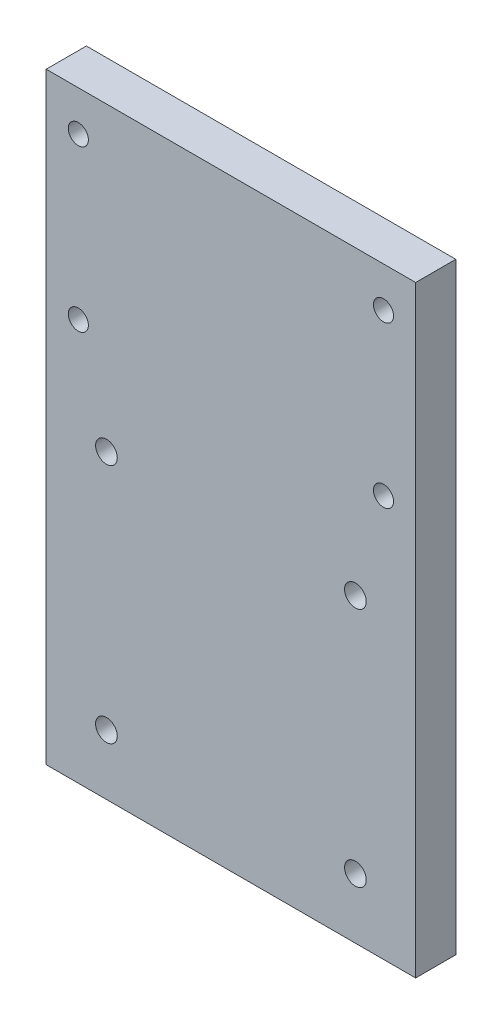
SolidWorks part; units mm, degrees
ref_plane "前基準面" through (0, 0, 0) normal (0, 0, 1) x (1, 0, 0)
ref_plane "上基準面" through (0, 0, 0) normal (0, 1, 0) x (1, 0, 0)
ref_plane "右基準面" through (0, 0, 0) normal (1, 0, 0) x (0, 0, -1)
ref_axis "基準軸1" through (0, -55, 0) along (0, 1, 0)
ref_axis "基準軸2" through (-88.99, 0, 0) along (1, 0, 0)
ref_axis "基準軸3" through (0, 0, 55) along (0, 0, -1)
sketch "草圖1" plane through (0, 0, 0) normal (0, 0, 1) x (1, 0, 0)
  line L0 (0, -41.25) -> (0, 41.25) construction
  line L1 (-23, -37.5) -> (23, -37.5)
  line L2 (-23, -37.5) -> (-23, 37.5)
  line L3 (-23, 37.5) -> (23, 37.5)
  line L4 (23, -37.5) -> (23, 37.5)
  line L5 (25.3, 0) -> (-25.3, 0) construction
  circle A0 centre (-19, 32.5) radius 1.25
  circle A1 centre (-15.5, -30) radius 1.35
  circle A2 centre (-15.5, 0) radius 1.35
  circle A3 centre (15.5, -30) radius 1.35
  circle A4 centre (15.5, 0) radius 1.35
  circle A5 centre (19, 32.5) radius 1.25
  circle A6 centre (-19, 12.5) radius 1.25
  circle A7 centre (19, 12.5) radius 1.25
  point P6 (0, 37.5)
  point P10 (23, 0)
  dimension "D3" = 2.5
  dimension "D6" = 2.7
  dimension "D9" = 2.7
  dimension "D12" = 2.5
  dimension "D1" = 46
  dimension "D2" = 75
  dimension "D4" = 5
  dimension "D5" = 4
  dimension "D7" = 7.5
  dimension "D8" = 7.5
  dimension "D10" = 30
  dimension "D11" = 7.5
  dimension "D13" = 4
  dimension "D14" = 20
extrude "填料-伸長1" add sketch "草圖1" along normal blind 5
